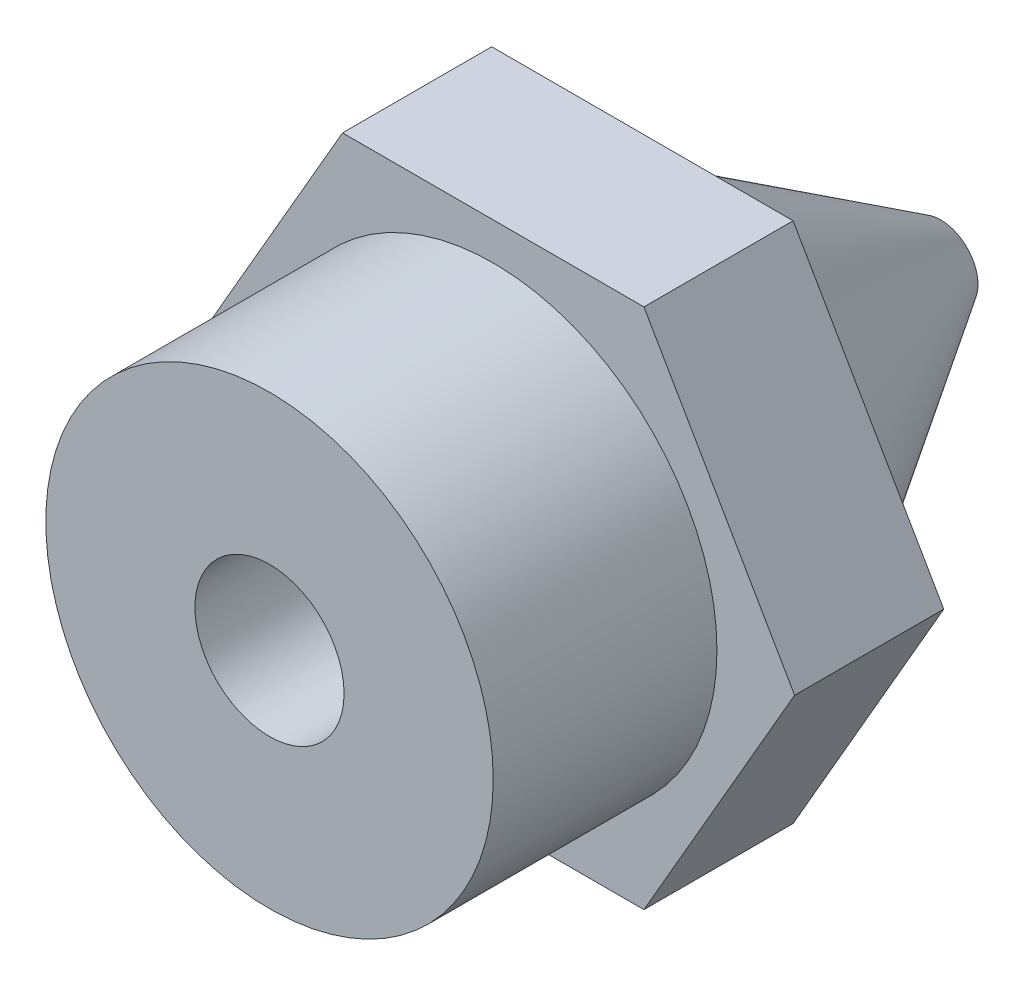
SolidWorks part; units mm, degrees
ref_plane "Plan de face" through (0, 0, 0) normal (0, 0, 1) x (1, 0, 0)
ref_plane "Plan de dessus" through (0, 0, 0) normal (0, 1, 0) x (1, 0, 0)
ref_plane "Plan de droite" through (0, 0, 0) normal (1, 0, 0) x (0, 0, -1)
sketch "Esquisse1" plane through (0, 0, 0) normal (0, 0, 1) x (1, 0, 0)
  line L1 (4.0415, 0) -> (2.0207, 3.5)
  line L2 (2.0207, 3.5) -> (-2.0207, 3.5)
  line L3 (-2.0207, 3.5) -> (-4.0415, 0)
  line L4 (-4.0415, 0) -> (-2.0207, -3.5)
  line L5 (-2.0207, -3.5) -> (2.0207, -3.5)
  line L6 (2.0207, -3.5) -> (4.0415, 0)
  circle A0 centre (0, 0) radius 3.5 construction
  dimension "D1" = 7
extrude "Boss.-Extru.1" add sketch "Esquisse1" along normal blind 9
sketch "Esquisse2" plane through (0, 0, 9) normal (0, 0, 1) x (1, 0, 0)
  line L1 (-7.9912, 5.5023) -> (7.566, 5.5023)
  line L2 (-7.9912, 5.5023) -> (-7.9912, -5.9665)
  line L3 (-7.9912, -5.9665) -> (7.566, -5.9665)
  line L4 (7.566, 5.5023) -> (7.566, -5.9665)
  circle A0 centre (0, 0) radius 3
  dimension "D1" = 6
extrude "Enlèv. mat.-Extru.1" cut sketch "Esquisse2" against normal blind 3
cosmetic thread "Représentation de filetage1" parameters "D2"=4.891
sketch "Esquisse3" plane through (0, 0, 0) normal (0, 0, -1) x (-1, 0, 0)
  line L1 (7.8656, -6.0768) -> (-7.4574, -6.0768)
  line L2 (7.8656, -6.0768) -> (7.8656, 5.7844)
  line L3 (7.8656, 5.7844) -> (-7.4574, 5.7844)
  line L4 (-7.4574, -6.0768) -> (-7.4574, 5.7844)
  circle A0 centre (0, 0) radius 3
  dimension "D1" = 6
extrude "Enlèv. mat.-Extru.3" cut sketch "Esquisse3" against normal blind 4
chamfer "Chanfrein2" distance 4 angle 32 1 edges at (-3, 0, 0) first distance on face at (-3, 0, 4)
sketch "Esquisse4" plane through (0, 0, 0) normal (0, 1, 0) x (1, 0, 0)
  line L0 (0, 0) -> (0, -9) construction
  line L1 (0.5005, 0) -> (-0.5005, 0) construction
  line L2 (-3, -9) -> (3, -9) construction
  line L3 (0, 0) -> (0.2, 0) construction
  line L4 (0, 1.4) -> (1, -6.6) construction
  line L5 (0, 0) -> (0, 1.4) construction
  line L6 (0.2, 0) -> (0.2, -1.4) construction
  line L7 (0.2, -1.4) -> (0, -1.4) construction
  line L8 (0, 1.4) -> (1, -6.6)
  line L9 (1, -6.6) -> (1, -9)
  line L10 (1, -9) -> (0, -9)
  line L11 (0, -9) -> (0, 1.4)
  dimension "D1" = 8
  dimension "D2" = 1
revolve "Enlèvement de matière-Révolution1" cut sketch "Esquisse4" angle 360 about L11
